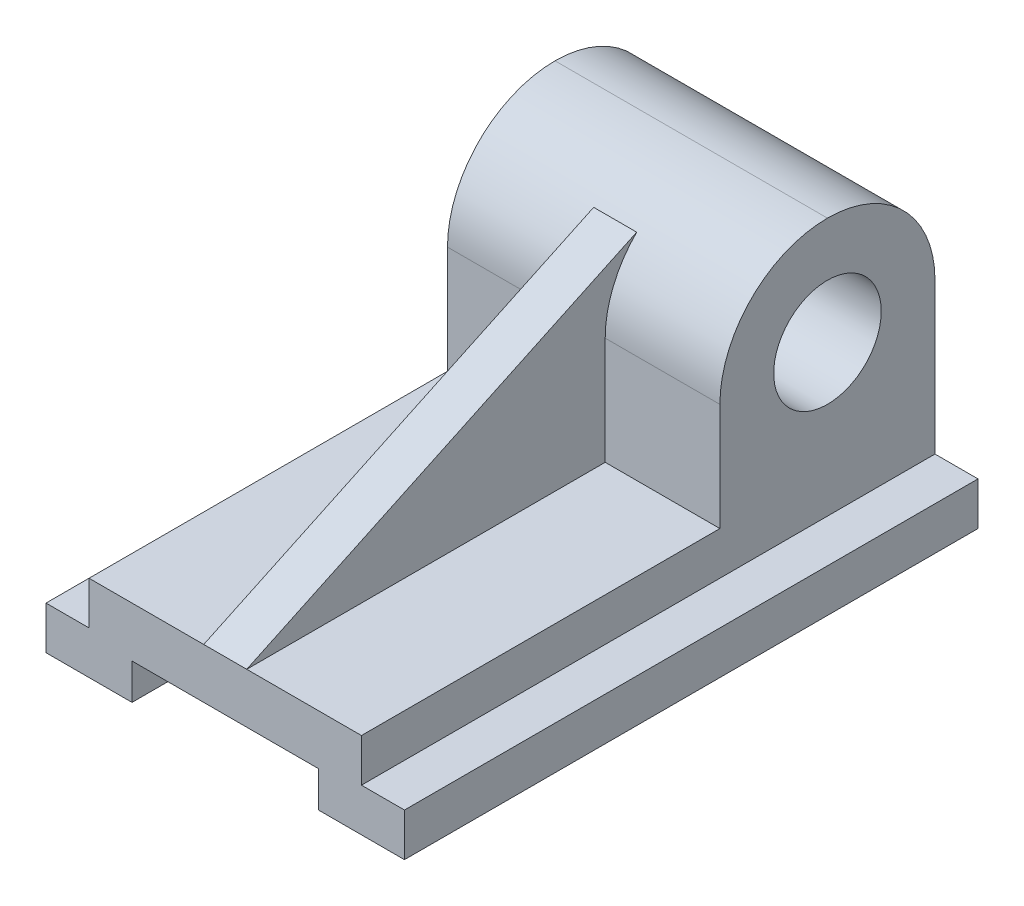
SolidWorks part; units mm, degrees
ref_plane "Front Plane" through (0, 0, 0) normal (0, 0, 1) x (1, 0, 0)
ref_plane "Top Plane" through (0, 0, 0) normal (0, 1, 0) x (1, 0, 0)
ref_plane "Right Plane" through (0, 0, 0) normal (1, 0, 0) x (0, 0, -1)
sketch "Sketch1" plane through (0, 0, 0) normal (0, 0, 1) x (1, 0, 0)
  line L4 (-38, 24) -> (38, 24)
  line L5 (38, 24) -> (38, 12)
  line L6 (38, 12) -> (50, 12)
  line L7 (50, 12) -> (50, 0)
  line L8 (50, 0) -> (26, 0)
  line L9 (26, 0) -> (26, 10)
  line L10 (26, 10) -> (-26, 10)
  line L12 (0, 0) -> (0, 34.8864) construction
  line L13 (-26, 0) -> (-26, 10)
  line L14 (-50, 12) -> (-50, 0)
  line L15 (-50, 0) -> (-26, 0)
  line L16 (-38, 12) -> (-50, 12)
  line L17 (-38, 24) -> (-38, 12)
  point P1 (0, 10)
  point P15 (0, 0)
  point P17 (0, 24)
  point P18 (0, 0)
  dimension "D1" = 52
  dimension "D2" = 10
  dimension "D3" = 100
  dimension "D4" = 12
  dimension "D5" = 24
  dimension "D7" = 12
extrude "Boss-Extrude1" add sketch "Sketch1" against normal blind 160
sketch "Sketch2" plane through (0, 24, 0) normal (0, 1, 0) x (1, 0, 0)
  line L0 (38, 160) -> (38, 0) construction
  line L1 (-38, 160) -> (38, 160)
  line L2 (-38, 160) -> (-38, 100)
  line L3 (-38, 100) -> (38, 100)
  line L4 (38, 160) -> (38, 100)
  dimension "D1" = 60
extrude "Boss-Extrude2" add sketch "Sketch2" along normal blind 60
fillet "Fillet1" radius 30 2 edges at (0, 84, -160) (0, 84, -100)
sketch "Sketch3" plane through (38, 0, 0) normal (1, 0, 0) x (0, 0, -1)
  line L0 (130, 84) -> (130, 24) construction
  line L1 (94.6056, 63.4294) -> (176.3688, 63.4294) construction
  circle A0 centre (130, 54) radius 15
  point P8 (0, 0)
  point P9 (0, 0)
  dimension "D1" = 30
  dimension "D2" = 42
extrude "Cut-Extrude1" cut sketch "Sketch3" against normal through all
sketch "Sketch7" plane through (0, 0, 0) normal (1, 0, 0) x (0, 0, -1)
  line L0 (0, 24) -> (108.7868, 75.2132)
  line L1 (100, 54) -> (100, 24) construction
  arc A0 (130, 84) -> (100, 54) centre (130, 54) ccw construction
rib "Rib1" sketch "Sketch7" sketch "Sketch7" thickness 12 extrusion direction parallel to sketch draft on no parameters "D1"=12
